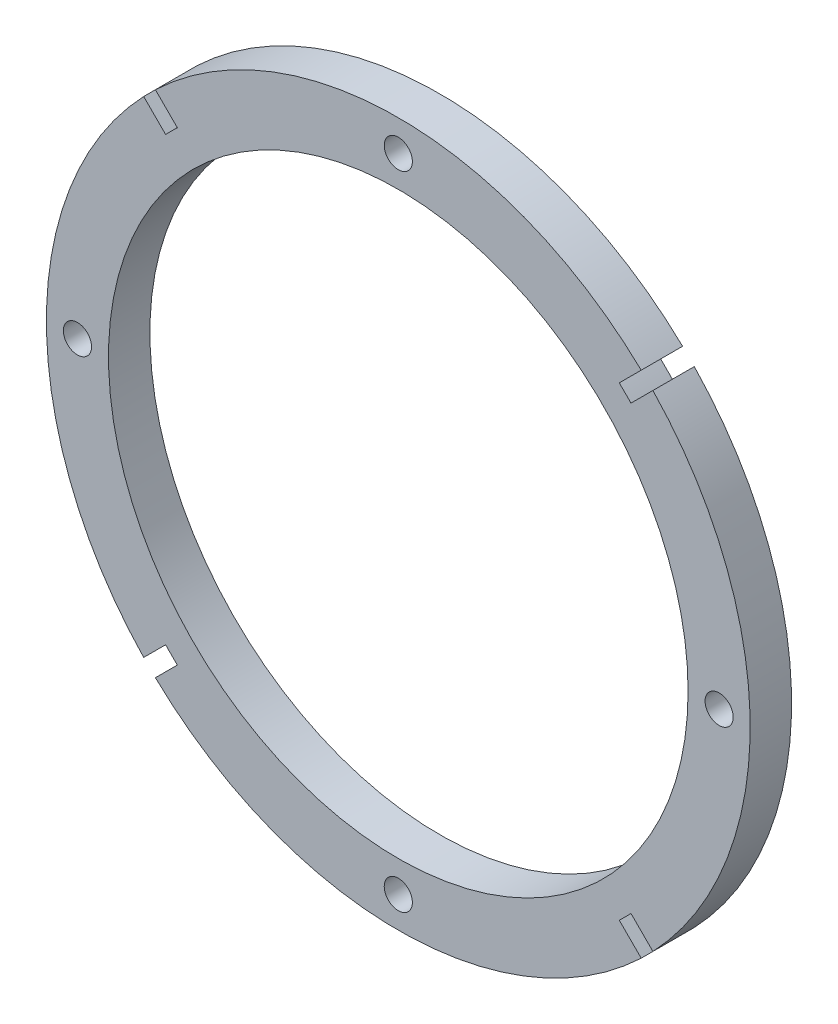
SolidWorks part; units mm, degrees
ref_plane "Płaszczyzna przednia" through (0, 0, 0) normal (0, 0, 1) x (1, 0, 0)
ref_plane "Płaszczyzna górna" through (0, 0, 0) normal (0, 1, 0) x (1, 0, 0)
ref_plane "Płaszczyzna prawa" through (0, 0, 0) normal (1, 0, 0) x (0, 0, -1)
sketch "Szkic1" plane through (0, 0, 0) normal (0, 0, 1) x (1, 0, 0)
  circle A0 centre (0, 0) radius 85
  circle A1 centre (0, 0) radius 70
  dimension "D1" = 140
  dimension "D2" = 170
extrude "Dodanie-wyciągnięcie1" add sketch "Szkic1" along normal blind 10 contours A1 | A0
sketch "Szkic2" plane through (0, 0, 10) normal (0, 0, 1) x (1, 0, 0)
  line L0 (0, 92.4389) -> (0, -92.4389) construction
  line L1 (0, 0) -> (-73.1252, 73.1252) construction
  line L3 (-56.1967, 53.3683) -> (-61.5016, 58.6732)
  line L4 (-53.3683, 56.1967) -> (-58.6732, 61.5016)
  line L6 (-1.4142, -1.4142) -> (-74.5394, 71.711) construction
  circle A0 centre (0, 77.5) radius 3.4
  circle A1 centre (0, 0) radius 70 construction
  arc A5 (-58.6732, 61.5016) -> (-61.5016, 58.6732) centre (0, 0) ccw
  arc A6 (-53.3683, 56.1967) -> (-56.1967, 53.3683) centre (0, 0) ccw
  point P7 (0, 0)
  point P10 (1.4142, 8.6364)
  point P11 (-71.711, 81.7616)
  point P20 (0, 0)
  dimension "D2" = 6.8
  dimension "D7" = 7.5
  dimension "D1" = 45
  dimension "D3" = 77.5
  dimension "D4" = 4
  dimension "D5" = 2
extrude "Wytnij-wyciągnięcie1" cut sketch "Szkic2" against normal blind 10
pattern_circular "Szyk kołowy1" count 4 over 360 about axis through (0, 0, 10) along (0, 0, -1) of "Wytnij-wyciągnięcie1" reverse direction yes
